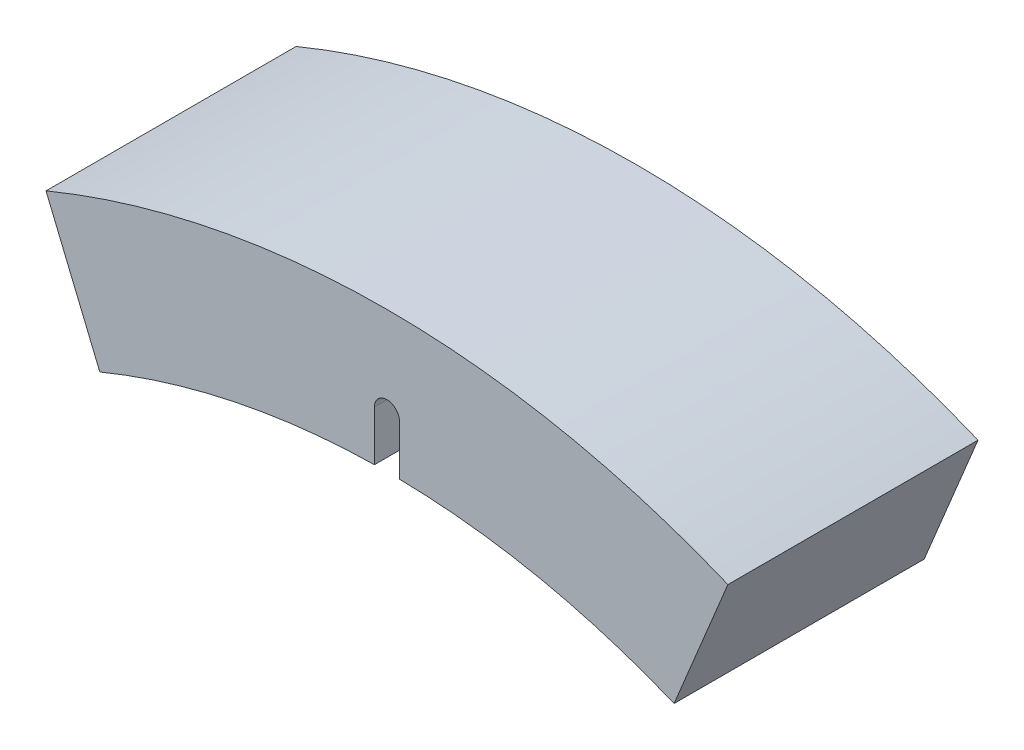
SolidWorks part; units mm, degrees
ref_plane "Front Plane" through (0, 0, 0) normal (0, 0, 1) x (1, 0, 0)
ref_plane "Top Plane" through (0, 0, 0) normal (0, 1, 0) x (1, 0, 0)
ref_plane "Right Plane" through (0, 0, 0) normal (1, 0, 0) x (0, 0, -1)
sketch "Sketch1" plane through (0, 0, 0) normal (0, 0, 1) x (1, 0, 0)
  line L0 (2, 0) -> (2, 128) construction
  line L1 (-2, 0) -> (-2, 128) construction
  line L2 (-2, 128) -> (-2, 1.5)
  line L3 (2, 128) -> (2, 1.5)
  circle A0 centre (0, 0) radius 1.5
  circle A1 centre (0, 0) radius 2.5 construction
  circle A2 centre (0, 0) radius 2 construction
  arc A4 (-2, 128) -> (2, 128) centre (0, 128) cw
  arc A5 (2, 1.5) -> (-2, 1.5) centre (0, 0) cw
  circle A7 centre (0, 128) radius 1.25
  dimension "D1" = 3
  dimension "D2" = 1
  dimension "D3" = 4
  dimension "D6" = 2.5
  dimension "D4" = 128
  dimension "D5" = 128
ref_plane "Plane1" through (0, 0, 11) normal (0, 0, 1) x (1, 0, 0)
sketch "Sketch2" plane through (0, 0, 11) normal (0, 0, 1) x (1, 0, 0)
  line L0 (0, 0) -> (0, 142.5) construction
  line L1 (0, 0) -> (-54.5324, 131.6528) construction
  line L4 (-2, 128) -> (-2, 1.5) construction
  line L5 (2, 1.5) -> (2, 128) construction
  line L6 (0, 0) -> (54.5324, 131.6528) construction
  line L7 (45.922, 110.8655) -> (54.5324, 131.6528)
  line L8 (-45.922, 110.8655) -> (-54.5324, 131.6528)
  line L9 (2, 119.9833) -> (2, 128)
  line L10 (-2, 128) -> (-2, 119.9833)
  circle A1 centre (0, 128) radius 1.25
  arc A4 (-2, 1.5) -> (2, 1.5) centre (0, 0) ccw construction
  arc A5 (2, 128) -> (-2, 128) centre (0, 128) ccw
  circle A6 centre (0, 0) radius 142.5 construction
  circle A7 centre (0, 0) radius 120 construction
  arc A8 (45.922, 110.8655) -> (-45.922, 110.8655) centre (0, 0) ccw
  arc A9 (54.5324, 131.6528) -> (-54.5324, 131.6528) centre (0, 0) ccw
  dimension "D2" = 285
  dimension "D4" = 240
  dimension "D3" = 22.5
extrude "Boss-Extrude3" add sketch "Sketch2" along normal blind 20 and the other way blind 20 contours L7 A9 L8 A8 L10 A5 L9 region at (24.6217, 118.6069, 11)
extrude "Boss-Extrude5" add sketch "Sketch2<8>" along normal blind 10 and the other way blind 10 contours A8 L9 A5 L10 A1 region at (0, 124.3217, 11)
sketch "Sketch2<8>" plane through (0, 0, 11) normal (0, 0, 1) x (1, 0, 0) same geometry as "Sketch2"
